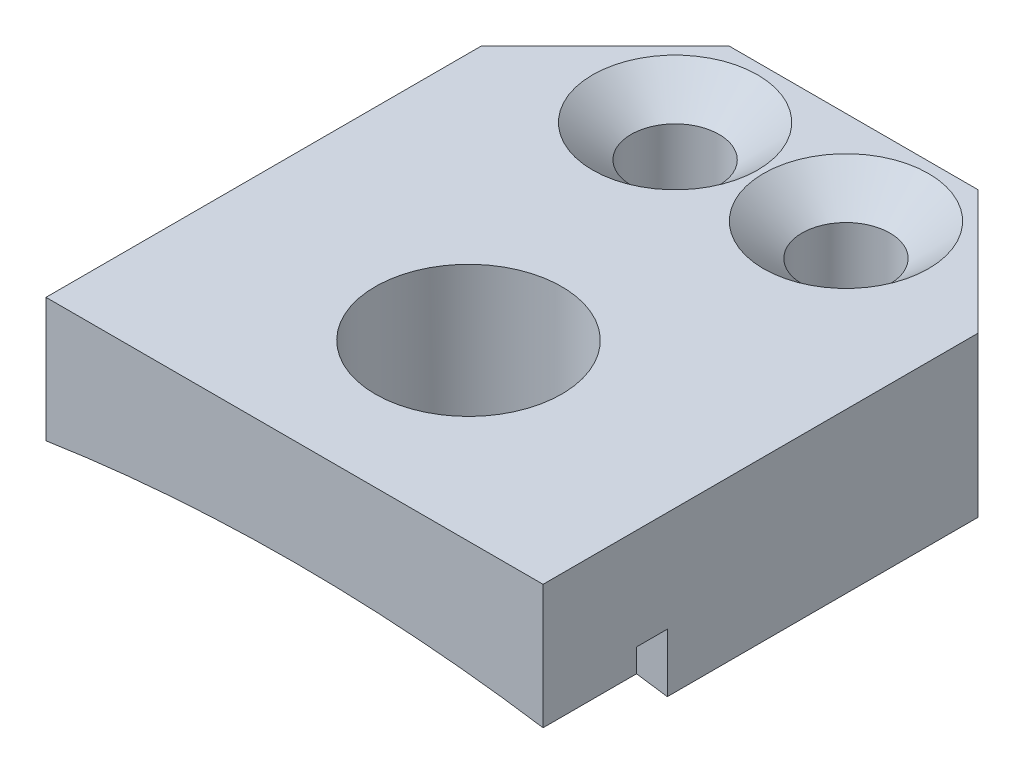
SolidWorks part; units mm, degrees
ref_plane "Front Plane" through (0, 0, 0) normal (0, 0, 1) x (1, 0, 0)
ref_plane "Top Plane" through (0, 0, 0) normal (0, 1, 0) x (1, 0, 0)
ref_plane "Right Plane" through (0, 0, 0) normal (1, 0, 0) x (0, 0, -1)
sketch "Sketch1" plane through (0, 0, 0) normal (0, 1, 0) x (1, 0, 0)
  line L0 (-28.5118, 9.6703) -> (-22.1618, 16.0203)
  line L1 (-22.1618, 16.0203) -> (-9.4618, 16.0203)
  line L2 (-28.5118, 9.6703) -> (-28.5118, -12.5547)
  line L3 (-28.5118, -12.5547) -> (-3.1118, -12.5547)
  line L4 (-3.1118, 9.6703) -> (-3.1118, -12.5547)
  line L5 (-9.4618, 16.0203) -> (-3.1118, 9.6703)
  line L6 (-15.8118, -12.5547) -> (-15.8118, 16.0203) construction
  line L8 (-3.1118, 9.6703) -> (-3.1118, 16.0203) construction
  line L9 (-3.1118, 16.0203) -> (-9.4618, 16.0203) construction
  dimension "D1" = 12.7
  dimension "D2" = 28.575
  dimension "D3" = 25.4
extrude "Boss-Extrude1" add sketch "Sketch1" along normal blind 6.35
sketch "Sketch2" plane through (0, 0, 12.5547) normal (0, 0, 1) x (1, 0, 0)
  circle A0 centre (-15.8118, -82.8523) radius 83.82
  dimension "D1" = 167.64
extrude "Cut-Extrude1" cut sketch "Sketch2" against normal through all both and the other way through all
sketch "Sketch5" plane through (0, 0, -16.0203) normal (0, 0, -1) x (-1, 0, 0)
  line L0 (3.1118, 6.35) -> (3.1118, 0) construction
  line L1 (3.1118, 6.35) -> (3.1118, 0)
  line L4 (28.5118, 6.35) -> (28.5118, 0) construction
  line L5 (28.5118, 6.35) -> (28.5118, 0)
  line L6 (28.5118, -1.7992) -> (28.5118, 0)
  line L7 (3.1118, -1.7992) -> (3.1118, 0)
  line L8 (3.1118, 6.35) -> (28.5118, 6.35)
  arc A0 (3.1118, -1.7992) -> (28.5118, -1.7992) centre (15.8118, -82.8523) cw
  arc A1 (28.5118, 0) -> (3.1118, 0) centre (15.8118, -82.8523) ccw construction
  arc A2 (28.5118, 0) -> (3.1118, 0) centre (15.8118, -82.8523) ccw construction
  dimension "D1" = 82.042
extrude "Boss-Extrude2" add sketch "Sketch5" against normal blind 22.225
chamfer "Chamfer1" distance 6.35 angle 45 2 edges at (-28.5118, 2.2754, -16.0203) (-3.1118, 2.2754, -16.0203)
hole_wizard "CSK for #8 Flat Head Machine Screw (100)1" positions "Sketch3" profile "Sketch4" countersink size "#8" standard "ANSI Inch" end condition through all
sketch "Sketch3" plane through (0, 6.35, 0) normal (0, 1, 0) x (1, 0, 0)
  line L0 (-15.8118, 16.0203) -> (-15.8118, 3.4006) construction
  line L1 (-9.4618, 16.0203) -> (-22.1618, 16.0203) construction
  point P0 (-20.1775, 11.2578)
  point P12 (-11.4462, 11.2578)
  dimension "D1" = 4.7625
  dimension "D2" = 4.3656
sketch "Sketch4" plane through (-20.1775, 6.35, -11.2578) normal (1, 0, 0) x (0, 0, 1)
  line L0 (0, 0) -> (0, 8.1492)
  line L1 (0, 8.1492) -> (2.2479, 8.1492)
  line L2 (2.2479, 8.1492) -> (2.2479, 1.6518)
  line L3 (2.2479, 1.6518) -> (4.2164, 0)
  line L5 (4.2164, 0) -> (0, 0)
  line L6 (-2.2479, 1.6518) -> (-4.2164, 0) construction
  line L11 (0, -6.35) -> (0, 107.95) construction
  dimension "Thru Hole Dia." = 4.4958
  dimension "Thru Hole Depth" = 8.1492
  dimension "Near C'Sink Dia." = 8.4328
  dimension "Near C'Sink Angle" = 100
sketch "Sketch6" plane through (0, 6.35, 0) normal (0, 1, 0) x (1, 0, 0)
  line L0 (-9.4618, 16.0203) -> (-22.1618, 16.0203) construction
  line L1 (-15.8118, -12.5547) -> (-15.8118, 16.0203) construction
  line L2 (-28.5118, -12.5547) -> (-3.1118, -12.5547) construction
  circle A1 centre (-15.8118, -3.6647) radius 1.524
  point P9 (0, 0)
  dimension "D1" = 3.048
  dimension "D2" = 19.685
extrude "Cut-Extrude2" cut sketch "Sketch6" against normal through all
sketch "Sketch7" plane through (-3.1118, 0, 0) normal (1, 0, 0) x (0, 0, -1)
  line L1 (-6.2047, -1.7992) -> (-7.7922, -1.7992)
  line L2 (-6.2047, -1.7992) -> (-6.2047, 1.1906)
  line L3 (-6.2047, 1.1906) -> (-7.7922, 1.1906)
  line L4 (-7.7922, -1.7992) -> (-7.7922, 1.1906)
  line L5 (-6.2047, -1.7992) -> (9.6703, -1.7992) construction
  line L6 (-12.5547, 0) -> (-6.2047, 0) construction
  line L7 (-6.2047, 0) -> (-6.2047, -1.7992) construction
  dimension "D1" = 1.5875
  dimension "D2" = 1.1906
extrude "Cut-Extrude3" cut sketch "Sketch7" against normal through all
sketch "Sketch8" plane through (0, 6.35, 0) normal (0, 1, 0) x (1, 0, 0)
  circle A0 centre (-15.8118, -3.6647) radius 4.7625
  dimension "D1" = 9.525
extrude "Cut-Extrude4" cut sketch "Sketch8" against normal through all
